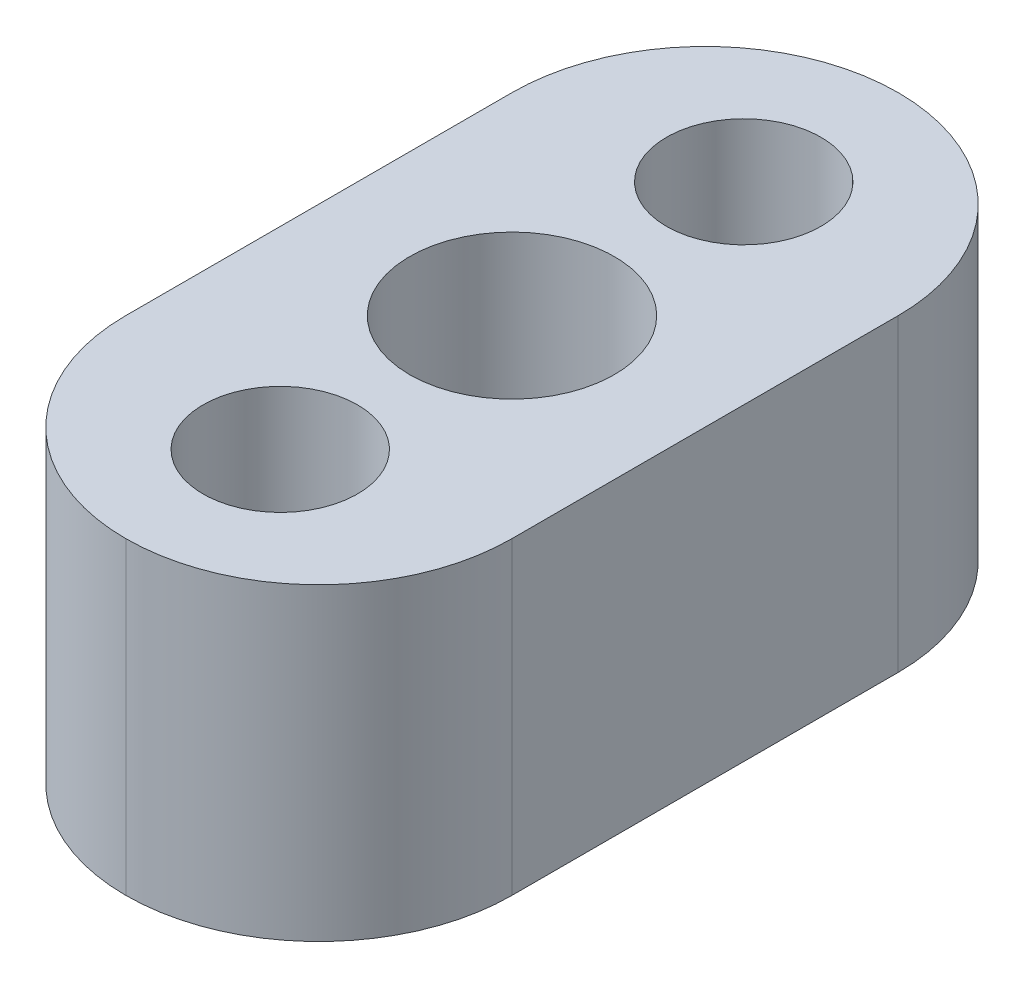
SolidWorks part; units mm, degrees
ref_plane "Plan de face" through (0, 0, 0) normal (0, 0, 1) x (1, 0, 0)
ref_plane "Plan de dessus" through (0, 0, 0) normal (0, 1, 0) x (1, 0, 0)
ref_plane "Plan de droite" through (0, 0, 0) normal (1, 0, 0) x (0, 0, -1)
sketch "Esquisse1" plane through (0, 0, 0) normal (0, 1, 0) x (1, 0, 0)
  line L0 (5, 20) -> (5, 0) construction
  line L1 (0, 0) -> (10, 0)
  line L2 (0, 0) -> (0, 20)
  line L3 (0, 20) -> (10, 20)
  line L4 (10, 0) -> (10, 20)
  line L5 (0, 10) -> (10, 10) construction
  circle A0 centre (5, 16) radius 2
  circle A1 centre (5, 4) radius 2
  dimension "D4" = 4
  dimension "D1" = 10
  dimension "D2" = 20
  dimension "D3" = 4
extrude "Boss.-Extru.1" add sketch "Esquisse1" along normal blind 8
sketch "Esquisse2" plane through (0, 8, 0) normal (0, 1, 0) x (1, 0, 0)
  line L0 (0, 20) -> (10, 0) construction
  circle A0 centre (5, 10) radius 2.65
  dimension "D1" = 5.3
extrude "Enlèv. mat.-Extru.1" cut sketch "Esquisse2" against normal blind 5
fillet "Congé1" radius 5 4 edges at (0, 4, 0) (10, 4, 0) (0, 4, -20) (10, 4, -20)
